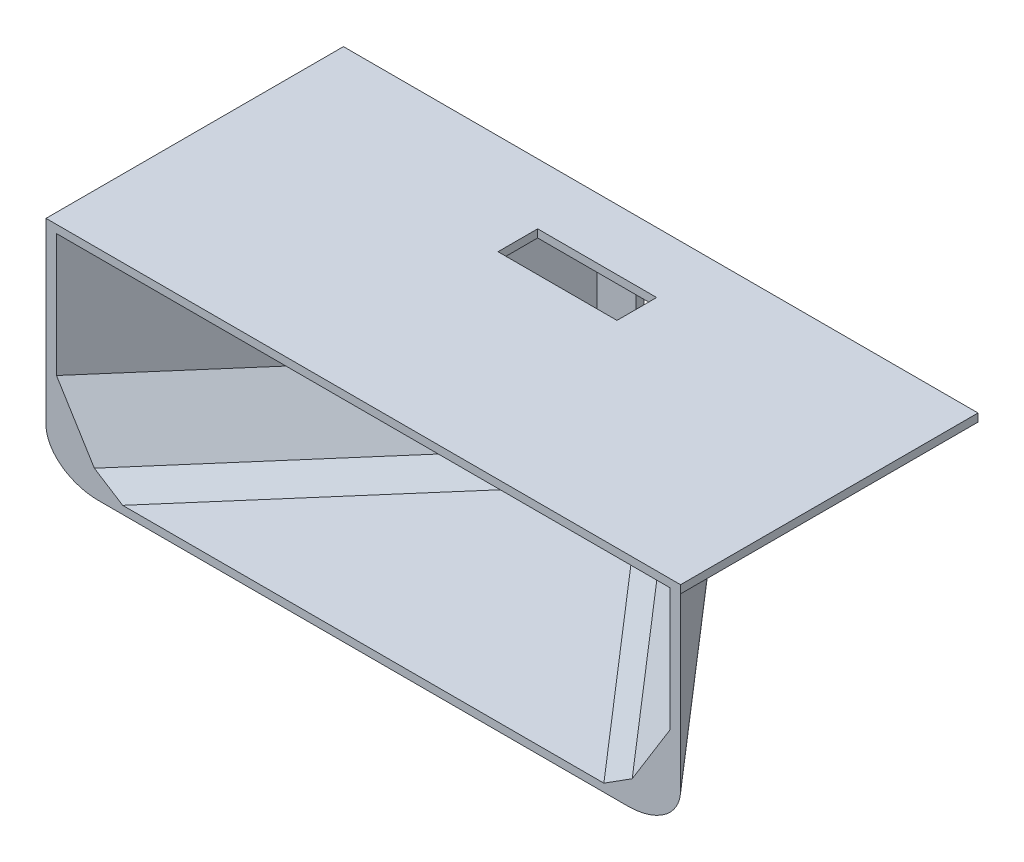
SolidWorks part; units mm, degrees
ref_plane "Front Plane" through (0, 0, 0) normal (0, 0, 1) x (1, 0, 0)
ref_plane "Top Plane" through (0, 0, 0) normal (0, 1, 0) x (1, 0, 0)
ref_plane "Right Plane" through (0, 0, 0) normal (1, 0, 0) x (0, 0, -1)
sketch "Sketch1" plane through (0, 0, 0) normal (0, 1, 0) x (1, 0, 0)
  line L0 (0, 0) -> (-160, 0)
  line L1 (-160, 0) -> (-94.9967, 75)
  line L2 (-94.9967, 75) -> (-64.9967, 75)
  line L3 (-64.9967, 75) -> (0, 0)
  dimension "D1" = 75
  dimension "D2" = 160
  dimension "D3" = 30
  dimension "D5" = 99.245
  dimension "D6" = 99.2493
extrude "Boss-Extrude1" add sketch "Sketch1" against normal blind 55
ref_plane "Plane6" through (-94.9967, 0, -75) normal (0, 1, 0) x (1, 0, 0)
shell "Shell1" thickness 2 removed face at (-80, -27.5, 0)
sketch "Sketch5" plane through (0, 0, -73) normal (0, 0, 1) x (1, 0, 0)
  line L0 (-65.91, -2) -> (-94.0835, -2) construction
  line L1 (-75.7485, -20.9978) -> (-84.2485, -20.9978)
  line L2 (-75.7485, -20.9978) -> (-75.7485, -12.5)
  line L3 (-75.7485, -12.5) -> (-84.2485, -12.5)
  line L4 (-84.2485, -20.9978) -> (-84.2485, -12.5)
  line L5 (-94.0835, -53) -> (-94.0835, -2) construction
  line L7 (-65.91, -53) -> (-65.91, -2) construction
  dimension "D1" = 9.835
  dimension "D2" = 8.5
  dimension "D3" = 10.5
  dimension "D4" = 9.8385
sketch "Sketch6" plane through (0, 0, 0) normal (0, 1, 0) x (1, 0, 0)
  line L1 (-95.447, 46.2243) -> (-65.447, 46.2243)
  line L2 (-95.447, 46.2243) -> (-95.447, 56.9342)
  line L3 (-95.447, 56.9342) -> (-65.447, 56.9342)
  line L4 (-65.447, 46.2243) -> (-65.447, 56.9342)
  dimension "D1" = 30
extrude "Cut-Extrude3" cut sketch "Sketch6" against normal blind 4
extrude "Cut-Extrude5" cut sketch "Sketch5" against normal blind 6
sketch "Sketch10" plane through (0, 0, 0) normal (0, 0, 1) x (1, 0, 0)
  line L0 (-160, -55) -> (-160, 0) construction
  line L1 (0, 0) -> (-160, 0)
  line L2 (0, 0) -> (0, -2)
  line L3 (0, -2) -> (-160, -2)
  line L4 (-160, 0) -> (-160, -2)
  dimension "D1" = 2
extrude "Boss-Extrude2" add sketch "Sketch10" against normal blind 75
sketch "Sketch11" plane through (0, -2, 0) normal (0, -1, 0) x (-1, 0, 0)
  line L14 (65.7295, 59.7) -> (95.7295, 59.7)
  line L15 (65.7295, 59.7) -> (65.7295, 49.7)
  line L16 (65.7295, 49.7) -> (95.7295, 49.7)
  line L17 (95.7295, 59.7) -> (95.7295, 49.7)
  dimension "D1" = 30
  dimension "D2" = 10
extrude "Cut-Extrude6" cut sketch "Sketch11" against normal blind 8
chamfer "Chamfer3" distance 20 angle 25 2 edges at (-125.7184, -53, -36.5) (-34.2783, -53, -36.5) first distance on face at (-125.7184, -27.5, -36.5) first distance on face at (-34.2783, -27.5, -36.5)
chamfer "Chamfer4" distance 15 angle 30 1 edges at (-79.9967, -55, -75) first distance on face at (-79.9983, -55, -37.5)
chamfer "Chamfer5" distance 20 angle 25 1 edges at (-79.9965, -53, -73) first distance on face at (-79.9985, -16.7489, -73)
chamfer "Chamfer9" distance 5 angle 25 3 edges at (-117.4184, -53, -31.8369) (-79.9969, -53, -63.6738) (-42.5781, -53, -31.8369) first distance on face at (-121.5684, -43, -34.1685) first distance on face at (-79.9968, -43, -68.3369) first distance on face at (-38.4282, -43, -34.1685)
fillet "Fillet1" radius 10 2 edges at (-25.9987, -55, -30) (-133.9987, -55, -30)
fillet "Fillet2" radius 10 1 edges at (-79.9967, -46.3397, -75)
